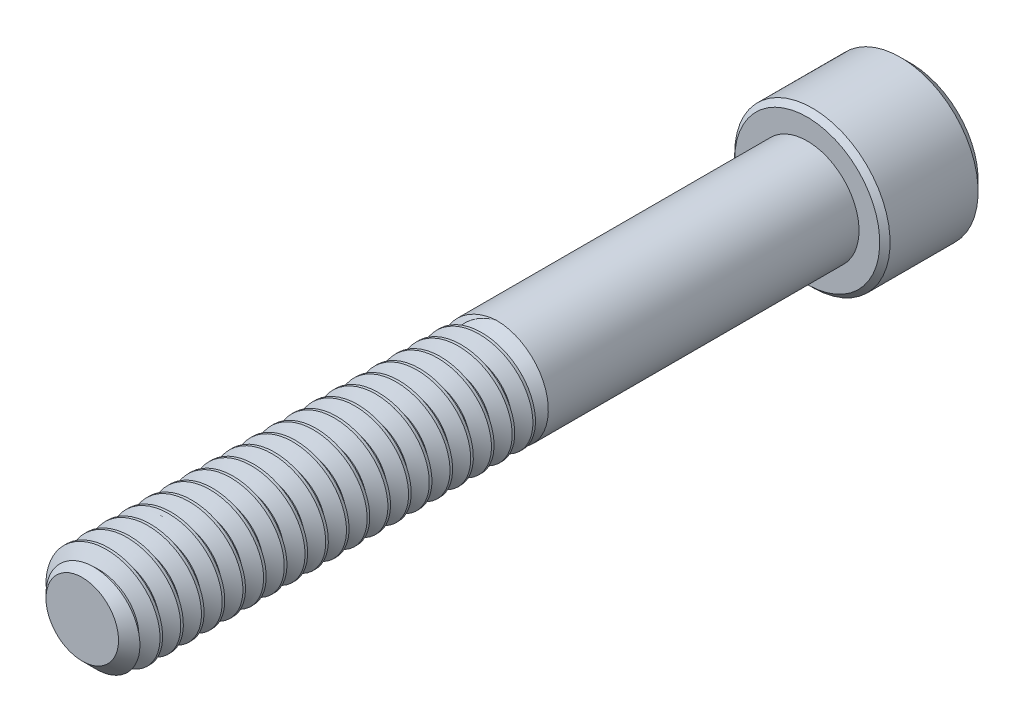
SolidWorks part; units mm, degrees
material "Cast Alloy Steel"
ref_plane "Front Plane" through (0, 0, 0) normal (0, 0, 1) x (1, 0, 0)
ref_plane "Top Plane" through (0, 0, 0) normal (0, 1, 0) x (1, 0, 0)
ref_plane "Right Plane" through (0, 0, 0) normal (1, 0, 0) x (0, 0, -1)
sketch "Sketch1" plane through (0, 0, 0) normal (0, 0, 1) x (1, 0, 0)
  line L0 (0, 3.175) -> (0, -3.175) construction
  circle A0 centre (0, 0) radius 3.175
  dimension "OD" = 6.35
extrude "Extrude1" add sketch "Sketch1" against normal blind 44.45
sketch "Sketch2" plane through (0, 0, 0) normal (0, 0, 1) x (1, 0, 0)
  circle A0 centre (0, 0) radius 3.175 construction
  circle A1 centre (0, 0) radius 3.175
curve "Helix/Spiral1" pitch 1.27 height 27.94 turns 22 parameters "pitch"=1.27
chamfer "Chamfer3" distance 0.9525 angle 45 1 edges at (3.175, 0, 0)
sketch "Sketch3" plane through (0, 0, 0) normal (1, 0, 0) x (0, 0, -1)
  line L0 (-1.1112, 3.175) -> (-0.635, 2.3501)
  line L1 (-0.635, 2.3501) -> (-0.4763, 2.3501)
  line L2 (-0.4763, 2.3501) -> (0, 3.175)
  line L3 (-1.1112, 3.175) -> (0, 3.175)
  line L4 (-0.5556, 3.175) -> (-0.5556, 2.3501) construction
  line L5 (-0.8731, 2.7626) -> (-0.2381, 2.7626) construction
  line L6 (0, 3.175) -> (0, -3.175) construction
  dimension "D1" = 0.1588
  dimension "D2" = 0.635
  dimension "D3" = 60
sweep "Cut-Sweep1" cut profiles "Sketch3" path "Helix/Spiral1"
sketch "Sketch5" plane through (0, 0, 0) normal (1, 0, 0) x (0, 0, -1)
  line L1 (44.45, 3.175) -> (25.4, 3.175)
  line L2 (44.45, 3.175) -> (44.45, 0)
  line L3 (44.45, 0) -> (25.4, 0)
  line L4 (25.4, 3.175) -> (25.4, 0) construction
  line L6 (0, 0) -> (9.9695, 0) construction
  line L8 (25.4, 3.175) -> (22.225, 0)
  line L9 (22.225, 0) -> (25.4, 0)
  line L10 (44.45, -3.175) -> (44.45, 3.175) construction
  dimension "D1" = 45
  dimension "Thread min" = 25.4
revolve "partially thread" add sketch "Sketch5" angle 360 about L6
sketch "Sketch6" plane through (0, 0, -44.45) normal (0, 0, -1) x (-1, 0, 0)
  circle A0 centre (0, 0) radius 4.7625
  dimension "head dia" = 9.525
extrude "Extrude2" add sketch "Sketch6" along normal blind 6.35
sketch "Sketch7" plane through (0, 0, -50.8) normal (0, 0, -1) x (-1, 0, 0)
  line L1 (0, 2.7496) -> (-2.3812, 1.3748)
  line L2 (-2.3812, 1.3748) -> (-2.3813, -1.3748)
  line L3 (-2.3813, -1.3748) -> (0, -2.7496)
  line L4 (0, -2.7496) -> (2.3813, -1.3748)
  line L5 (2.3813, -1.3748) -> (2.3813, 1.3748)
  line L6 (2.3813, 1.3748) -> (0, 2.7496)
  circle A0 centre (0, 0) radius 2.3813 construction
  dimension "hex dia" = 4.7625
extrude "Cut-Extrude1" cut sketch "Sketch7" against normal blind 3.5719
sketch "Sketch8" plane through (0, 0, -50.8) normal (0, 0, -1) x (-1, 0, 0)
  circle A0 centre (0, 0) radius 2.7496
extrude "Cut-Extrude2" cut sketch "Sketch8" against normal blind 0.635 draft 45
chamfer "Chamfer1" distance 0.635 angle 45 1 edges at (-4.7625, 0, -50.8)
chamfer "Chamfer2" distance 0.3175 angle 45 1 edges at (-4.7625, 0, -44.45)
sketch "Sketch9" plane through (0, 0, 0) normal (1, 0, 0) x (0, 0, -1)
  line L0 (0, 3.175) -> (0, -3.175) construction
  line L1 (6.985, 3.175) -> (6.985, -3.175) construction
  line L2 (44.45, 4.7625) -> (44.45, -4.7625) construction
  line L3 (50.8, 4.7625) -> (50.8, -4.7625) construction
  line L4 (50.8, 0) -> (0, 0) construction
  line L5 (61.6852, 3.175) -> (61.6852, -3.175) construction
  dimension "D1" = 6.985
  dimension "D2" = 6.35
  dimension "D3" = 9.525
  dimension "D4" = 44.45
  dimension "Thread Length" = 61.6852
equation "\"D3@Helix/Spiral1\" = \"Thread min@Sketch5\"+(\"pitch@Helix/Spiral1\"*2)"
equation "\"D1@Sketch3\" = \"pitch@Helix/Spiral1\"*.125"
equation "\"D2@Sketch3\" = \"pitch@Helix/Spiral1\"*.5"
equation "\"D1@Cut-Extrude1\" = \"hex dia@Sketch7\"*.75"
equation "\"D1@Chamfer1\" = \"head depth@Extrude2\"/10"
equation "\"D1@Sketch9\" = \"pitch@Helix/Spiral1\"*5.5"
equation "\"D1@Chamfer2\" = \"D1@Chamfer1\"/2"
equation "\"D1@Cut-Extrude2\" = \"D1@Chamfer2\"*2"
equation "\"D1@Chamfer3\" = \"pitch@Helix/Spiral1\"*.750"
equation "\"D2@Sketch9\" = \"head depth@Extrude2\""
equation "\"D3@Sketch9\" = \"head dia@Sketch6\""
equation "\"D4@Sketch9\" = \"screw length@Extrude1\""
